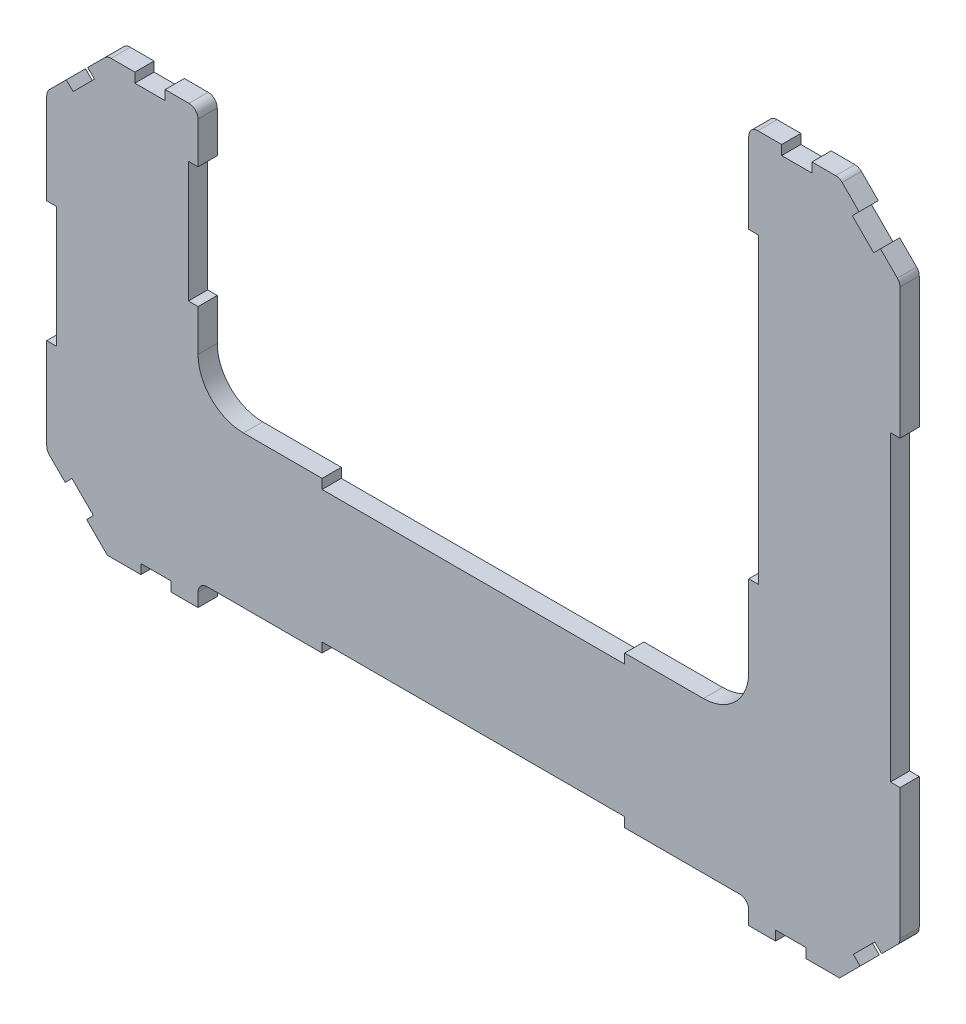
SolidWorks part; units mm, degrees
material "Cedar"
ref_plane "Front Plane" through (0, 0, 0) normal (0, 0, 1) x (1, 0, 0)
ref_plane "Top Plane" through (0, 0, 0) normal (0, 1, 0) x (1, 0, 0)
ref_plane "Right Plane" through (0, 0, 0) normal (1, 0, 0) x (0, 0, -1)
sketch "Sketch2" plane through (0, 0, 0) normal (0, 0, 1) x (1, 0, 0)
  line L0 (-141, 85.3385) -> (-91, 85.3385)
  line L1 (-91, 85.3385) -> (-91, 0)
  line L2 (-91, 0) -> (91, 0)
  line L3 (91, 0) -> (91, 171.5)
  line L4 (91, 171.5) -> (141, 171.5)
  line L5 (141, 171.5) -> (141, -57.5)
  line L6 (141, -57.5) -> (91, -57.5)
  line L7 (91, -57.5) -> (91, -50)
  line L8 (91, -50) -> (-91, -50)
  line L9 (-91, -50) -> (-91, -57.5)
  line L10 (-91, -57.5) -> (-141, -57.5)
  line L11 (-141, -57.5) -> (-141, 85.3385)
  line L12 (-31, 0) -> (-31, 124) construction
  point P10 (-31, 0)
  point P14 (91, 124)
  point P15 (-31, 85.3385)
  dimension "D1" = 124
  dimension "D2" = 122
  dimension "D3" = 60
  dimension "D4" = 47.5
  dimension "D5" = 50
  dimension "D6" = 50
  dimension "D7" = 7.5
extrude "Boss-Extrude1" add sketch "Sketch2" along normal blind 3.175 and the other way blind 3.175
chamfer "Chamfer1" distance 20 angle 45 4 edges at (-141, -57.5, 0) (141, -57.5, 0) (141, 171.5, 0) (-141, 85.3385, 0)
fillet "Fillet1" radius 15 2 edges at (91, 0, 0) (-91, 0, 0)
fillet "Fillet2" radius 3 10 edges at (141, -37.5, 0) (91, -50, 0) (-91, -50, 0) (-141, -37.5, 0) (-141, 65.3385, 0) (-121, 85.3385, 0) (-91, 85.3385, 0) (141, 151.5, 0) (121, 171.5, 0) (91, 171.5, 0)
sketch "Sketch3" plane through (0, 0, 3.175) normal (0, 0, 1) x (1, 0, 0)
  line L0 (-94.6381, 69.9757) -> (-94.6381, 14.7992)
  line L1 (-94.6381, 14.7992) -> (-97.8131, 14.7992)
  line L2 (-97.8131, 14.7992) -> (-97.8131, 69.9757)
  line L3 (-97.8131, 69.9757) -> (-94.6381, 69.9757)
  line L4 (-127.4635, 65.4691) -> (-114.3536, 78.579)
  line L5 (-114.3536, 78.579) -> (-112.1085, 76.3339)
  line L6 (-112.1085, 76.3339) -> (-125.2184, 63.2241)
  line L7 (-125.2184, 63.2241) -> (-127.4635, 65.4691)
  line L8 (-129.3392, 54.7846) -> (-126.1642, 54.7846)
  line L9 (-126.1642, 54.7846) -> (-126.1642, -28.3138)
  line L10 (-126.1642, -28.3138) -> (-129.3392, -28.3138)
  line L11 (-129.3392, -28.3138) -> (-129.3392, 54.7846)
  line L12 (-127.4635, -37.1329) -> (-125.2184, -34.8879)
  line L13 (-125.2184, -34.8879) -> (-110.9382, -49.1681)
  line L14 (-110.9382, -49.1681) -> (-113.1832, -51.4132)
  line L15 (-113.1832, -51.4132) -> (-127.4635, -37.1329)
  line L16 (-67.7784, -44.3183) -> (-67.7784, -41.1433)
  line L17 (-67.7784, -41.1433) -> (53.0181, -41.1433)
  line L18 (53.0181, -41.1433) -> (53.0181, -44.3183)
  line L19 (53.0181, -44.3183) -> (-67.7784, -44.3183)
  line L20 (114.9313, -49.5303) -> (117.1763, -51.7753)
  line L21 (117.1763, -51.7753) -> (131.7883, -37.1634)
  line L22 (131.7883, -37.1634) -> (129.5432, -34.9183)
  line L23 (129.5432, -34.9183) -> (114.9313, -49.5303)
  line L24 (-67.7784, -4.1746) -> (-67.7784, -7.3496)
  line L25 (-67.7784, -7.3496) -> (63.5847, -7.3496)
  line L26 (63.5847, -7.3496) -> (63.5847, -4.1746)
  line L27 (63.5847, -4.1746) -> (-67.7784, -4.1746)
  line L28 (92.7516, 20.9162) -> (91.2159, 151.9937)
  line L29 (91.2159, 151.9937) -> (94.3909, 151.9937)
  line L30 (94.3909, 151.9937) -> (95.9266, 20.9162)
  line L31 (95.9266, 20.9162) -> (92.7516, 20.9162)
  line L32 (96.8341, 161.8762) -> (96.8341, 158.7012)
  line L33 (96.8341, 158.7012) -> (112.5649, 158.7012)
  line L34 (112.5649, 158.7012) -> (112.5649, 161.8762)
  line L35 (112.5649, 161.8762) -> (96.8341, 161.8762)
  line L37 (117.7781, 156.4535) -> (120.0231, 158.6985)
  line L38 (120.0231, 158.6985) -> (133.8694, 144.8523)
  line L39 (133.8694, 144.8523) -> (131.6243, 142.6072)
  line L40 (131.6243, 142.6072) -> (117.7781, 156.4535)
  line L41 (129.9213, 134.1701) -> (133.0963, 134.1701)
  line L42 (133.0963, 134.1701) -> (133.0963, -24.961)
  line L43 (133.0963, -24.961) -> (129.9213, -24.961)
  line L44 (129.9213, -24.961) -> (129.9213, 134.1701)
  line L45 (121, -57.5) -> (140.1213, -38.3787) construction
  line L46 (-140.1213, -38.3787) -> (-121, -57.5) construction
  line L47 (-121.8787, 84.4598) -> (-140.1213, 66.2171) construction
  line L48 (140.1213, 152.3787) -> (121.8787, 170.6213) construction
  dimension "D1" = 3.175
extrude "Cut-Extrude1" [suppressed] cut sketch "Sketch3" against normal through all
sketch "magnets" plane through (0, 0, 3.175) normal (0, 0, 1) x (1, 0, 0)
  point P0 (94.6751, 158.4052)
  point P1 (114.7572, -50)
  point P2 (131.9288, 140.6094)
  point P3 (131.9288, -32.8111)
  point P4 (0, -44.1618)
  point P5 (-114.0039, -50)
  point P6 (-130.8821, -32.8111)
  point P9 (-130.8821, 62.3605)
  point P10 (-93.5499, 79.7316)
  point P12 (0, -4.7392)
sketch "Sketch4" plane through (0, 0, 3.175) normal (0, 0, 1) x (1, 0, 0)
  line L0 (101.8787, 171.5) -> (101.8787, 168.325)
  line L1 (119.7574, 171.5) -> (94, 171.5) construction
  line L2 (101.8787, 168.325) -> (111.8787, 168.325)
  line L3 (111.8787, 168.325) -> (111.8787, 171.5)
  line L4 (127.4645, 165.0355) -> (125.2194, 162.7905)
  line L5 (140.1213, 152.3787) -> (121.8787, 170.6213) construction
  line L6 (125.2194, 162.7905) -> (132.2905, 155.7194)
  line L7 (132.2905, 155.7194) -> (134.5355, 157.9645)
  line L8 (91, 141.75) -> (94.175, 141.75)
  line L9 (91, 168.5) -> (91, 15) construction
  line L10 (94.175, 141.75) -> (94.175, 41.75)
  line L11 (94.175, 41.75) -> (91, 41.75)
  line L12 (141, 107) -> (137.825, 107)
  line L13 (141, -36.2574) -> (141, 150.2574) construction
  line L14 (137.825, 107) -> (137.825, 7)
  line L15 (137.825, 7) -> (141, 7)
  line L16 (-50, 0) -> (-50, -3.175)
  line L17 (76, 0) -> (-76, 0) construction
  line L18 (-50, -3.175) -> (50, -3.175)
  line L19 (50, -3.175) -> (50, 0)
  line L20 (-50, -50) -> (-50, -46.825)
  line L21 (-88, -50) -> (88, -50) construction
  line L22 (-50, -46.825) -> (50, -46.825)
  line L23 (50, -46.825) -> (50, -50)
  line L24 (-137.825, -6.0808) -> (-141, -6.0808)
  line L25 (-141, 64.0958) -> (-141, -36.2574) construction
  line L26 (-137.825, 33.9192) -> (-137.825, -6.0808)
  line L27 (-137.825, 33.9192) -> (-141, 33.9192)
  line L28 (-134.5355, 71.8029) -> (-132.2905, 69.5579)
  line L29 (-121.8787, 84.4598) -> (-140.1213, 66.2171) construction
  line L30 (-132.2905, 69.5579) -> (-125.2194, 76.6289)
  line L31 (-125.2194, 76.6289) -> (-127.4645, 78.874)
  line L32 (-111.8787, 85.3385) -> (-111.8787, 82.1635)
  line L33 (-94, 85.3385) -> (-119.7574, 85.3385) construction
  line L35 (-111.8787, 82.1635) -> (-101.8787, 82.1635)
  line L36 (-91, 68.6692) -> (-94.175, 68.6692)
  line L37 (-91, 15) -> (-91, 82.3385) construction
  line L38 (-94.175, 68.6692) -> (-94.175, 28.6692)
  line L39 (-94.175, 28.6692) -> (-91, 28.6692)
  line L40 (-109.875, -57.5) -> (-109.875, -54.325)
  line L41 (-121, -57.5) -> (-91, -57.5) construction
  line L42 (-109.875, -54.325) -> (-99.875, -54.325)
  line L43 (-99.875, -54.325) -> (-99.875, -57.5)
  line L44 (99.875, -57.5) -> (99.875, -54.325)
  line L45 (91, -57.5) -> (121, -57.5) construction
  line L46 (99.875, -54.325) -> (109.875, -54.325)
  line L47 (109.875, -54.325) -> (109.875, -57.5)
  line L48 (-134.8917, -43.6083) -> (-132.6466, -41.3632)
  line L49 (-140.1213, -38.3787) -> (-121, -57.5) construction
  line L50 (-132.6466, -41.3632) -> (-125.5756, -48.4343)
  line L51 (-125.5756, -48.4343) -> (-127.8206, -50.6794)
  line L52 (127.8206, -50.6794) -> (125.5756, -48.4343)
  line L53 (121, -57.5) -> (140.1213, -38.3787) construction
  line L54 (125.5756, -48.4343) -> (132.6466, -41.3632)
  line L55 (132.6466, -41.3632) -> (134.8917, -43.6083)
  line L56 (-131.3562, -47.1438) -> (-129.1111, -44.8988) construction
  line L57 (-104.875, -57.5) -> (-104.875, -54.325)
  line L58 (104.875, -57.5) -> (104.875, -54.325)
  line L59 (-131, 75.3385) -> (-128.7549, 73.0934) construction
  line L60 (-106.8787, 82.1635) -> (-106.8787, 85.3385) construction
  line L61 (128.7549, 159.2549) -> (131, 161.5) construction
  line L62 (129.1111, -44.8988) -> (131.3562, -47.1438) construction
  line L63 (91, -57.5) -> (118.75, -57.5) construction
  line L64 (122.591, -55.909) -> (140.1213, -38.3787) construction
  line L65 (122.591, -55.909) -> (121, -57.5) construction
  line L66 (121, -57.5) -> (118.75, -57.5) construction
  line L67 (-91, -57.5) -> (-118.75, -57.5) construction
  line L68 (-118.75, -57.5) -> (-121, -57.5) construction
  line L69 (-121, -57.5) -> (-122.591, -55.909) construction
  line L70 (-122.591, -55.909) -> (-140.1213, -38.3787) construction
  line L71 (-101.8787, 82.1635) -> (-101.8787, 85.3385)
  point P95 (0, -46.825)
  point P97 (0, -50)
  point P99 (0, -3.175)
  point P101 (137.825, 57)
  point P103 (141, 57)
  point P104 (94.175, 91.75)
  point P105 (91, 91.75)
  point P106 (106.8787, 168.325)
  point P107 (106.8787, 171.5)
  point P108 (131, 161.5)
  point P109 (128.7549, 159.2549)
  point P112 (-137.825, 13.9192)
  point P113 (-141, 13.9192)
  point P114 (-94.175, 48.6692)
  point P115 (-91, 48.6692)
  point P116 (129.1111, -44.8988)
  point P117 (130.5607, -47.9393)
  line M1 (121, -57.5) -> (140.1213, -38.3787)
  line M3 (141, -36.2574) -> (141, 150.2574)
  line M5 (140.1213, 152.3787) -> (121.8787, 170.6213)
  line M7 (119.7574, 171.5) -> (94, 171.5)
  line M9 (91, 168.5) -> (91, 15)
  line M11 (76, 0) -> (-76, 0)
  line M13 (-91, 15) -> (-91, 82.3385)
  line M15 (-94, 85.3385) -> (-119.7574, 85.3385)
  line M17 (-121.8787, 84.4598) -> (-140.1213, 66.2171)
  line M19 (-141, 64.0958) -> (-141, -36.2574)
  line M21 (-140.1213, -38.3787) -> (-121, -57.5)
  line M22 (-121, -57.5) -> (-91, -57.5)
  line M25 (-88, -50) -> (88, -50)
  line M28 (91, -57.5) -> (121, -57.5)
  dimension "D1" = 3.175
  dimension "D5" = 100
  dimension "D6" = 100
  dimension "D7" = 100
  dimension "D8" = 100
  dimension "D4" = 10
  dimension "D2" = 10
  dimension "D10" = 2.25
  dimension "D3" = 2.25
  dimension "D11" = 10
  dimension "D13" = 3.175
  dimension "D12" = 10
  dimension "D14" = 10
  dimension "D15" = 10
  dimension "D16" = 10
  dimension "D17" = 10
  dimension "D18" = 40
  dimension "D19" = 3.175
extrude "wall_slots" cut sketch "Sketch4" against normal blind 60 contours L26 L27 L24 M19 | L18 L19 L16 M11 | L23 L22 L20 M25 | L51 L50 L48 M21 | L57 L43 L42 M22 | L57 L42 L40 M22 | L38 L39 L36 M13 | L35 L71 L32 M15 | L30 L31 L28 M17 | L58 L47 L46 M28 | L58 L46 L44 M28 | L55 L54 L52 M1 | L14 L15 L12 M3 | L11 L10 L8 M9 | L2 L3 L0 M7 | L6 L7 L4 M5 region at (106.8787, 169.9125, 3.175) region at (129.8775, 160.3775, 3.175) region at (92.5875, 91.75, 3.175) region at (139.4125, 57, 3.175) region at (0, -1.5875, 3.175) region at (0, -48.4125, 3.175) region at (-139.4125, 13.9192, 3.175) region at (-129.8775, 74.2159, 3.175) region at (-106.8787, 83.751, 3.175) region at (-92.5875, 48.6692, 3.175) region at (-130.2336, -46.0213, 3.175) region at (-107.375, -55.9125, 3.175) region at (-102.375, -55.9125, 3.175) region at (130.2336, -46.0213, 3.175) region at (102.375, -55.9125, 3.175) region at (107.375, -55.9125, 3.175)
sketch "wall_measure" plane through (0, 0, 3.175) normal (0, 0, 1) x (1, 0, 0)
  line L0 (-119.7574, 85.3385) -> (-119.7574, 82.1635)
  line L1 (-119.7574, 82.1635) -> (-94, 82.1635)
  line L2 (-94, 82.1635) -> (-94, 85.3385)
  line L4 (94, 171.5) -> (94, 168.325)
  line L5 (94, 168.325) -> (119.7574, 168.325)
  line L6 (119.7574, 168.325) -> (119.7574, 171.5)
  line L7 (101.8787, 168.325) -> (111.8787, 168.325) construction
  line L8 (121.8787, 170.6213) -> (119.6336, 168.3763)
  line L9 (119.6336, 168.3763) -> (137.8763, 150.1336)
  line L10 (137.8763, 150.1336) -> (140.1213, 152.3787)
  line L11 (140.1213, 152.3787) -> (134.5355, 157.9645) construction
  line L12 (91, 168.5) -> (94.175, 168.5)
  line L13 (94.175, 168.5) -> (94.175, 15)
  line L14 (94.175, 15) -> (91, 15)
  line L15 (91, 41.75) -> (91, 15) construction
  line L16 (141, 150.2574) -> (137.825, 150.2574)
  line L17 (137.825, 150.2574) -> (137.825, -36.2574)
  line L18 (137.825, -36.2574) -> (141, -36.2574)
  line L19 (-76, 0) -> (-76, -3.175)
  line L20 (-76, -3.175) -> (76, -3.175)
  line L21 (76, -3.175) -> (76, 0)
  line L22 (-88, -50) -> (-88, -46.825)
  line L23 (-88, -46.825) -> (88, -46.825)
  line L24 (88, -46.825) -> (88, -50)
  line L25 (91, -53) -> (117.9584, -53)
  line L26 (117.9584, -53) -> (117.9584, -57.5)
  line L27 (140.1213, -38.3787) -> (137.8763, -36.1336)
  line L28 (137.8763, -36.1336) -> (120.9057, -53.1042)
  line L29 (120.9057, -53.1042) -> (123.1508, -55.3492)
  line L30 (121, -57.5) -> (127.8206, -50.6794) construction
  line L31 (125.5756, -48.4343) -> (132.6466, -41.3632) construction
  line L32 (117.9584, -57.5) -> (121, -57.5) construction
  line L33 (121, -57.5) -> (123.1508, -55.3492) construction
  line L34 (-141, 64.0958) -> (-138, 64.0958)
  line L35 (-138, 64.0958) -> (-138, -36.2574)
  line L36 (-138, -36.2574) -> (-141, -36.2574)
  line L37 (-91, 82.3385) -> (-94.175, 82.3385)
  line L38 (-94.175, 82.3385) -> (-94.175, 15)
  line L39 (-94.175, 15) -> (-91, 15)
  line L40 (-50, -46.825) -> (50, -46.825) construction
  line L41 (-50, -3.175) -> (50, -3.175) construction
  line L42 (137.825, 107) -> (137.825, 7) construction
  line L43 (94.175, 141.75) -> (94.175, 41.75) construction
  line L44 (125.2194, 162.7905) -> (132.2905, 155.7194) construction
  line L45 (-94.175, 68.6692) -> (-94.175, 28.6692) construction
  line L47 (-111.8787, 82.1635) -> (-101.8787, 82.1635) construction
  arc A0 (76, 0) -> (91, 15) centre (76, 15) ccw construction
  arc A1 (-91, 15) -> (-76, 0) centre (-76, 15) ccw construction
  dimension "D1" = 25.7574
  dimension "D2" = 25.7574
  dimension "D3" = 25.799
  dimension "D4" = 153.5
  dimension "D5" = 186.5147
  dimension "D6" = 152
  dimension "D7" = 176
  dimension "D8" = 24
  dimension "D9" = 3.0416
  dimension "D10" = 26.9584
  dimension "D11" = 100.3532
  dimension "D12" = 67.3385
sketch "Sketch5" plane through (0, 0, 3.175) normal (0, 0, 1) x (1, 0, 0)
  line L72 (132.2905, 155.7194) -> (125.2194, 162.7905)
  line L73 (125.2194, 162.7905) -> (127.4645, 165.0355)
  line L74 (127.4645, 165.0355) -> (121.8787, 170.6213)
  line L75 (119.7574, 171.5) -> (111.8787, 171.5)
  line L76 (111.8787, 171.5) -> (111.8787, 168.325)
  line L77 (111.8787, 168.325) -> (101.8787, 168.325)
  line L78 (101.8787, 168.325) -> (101.8787, 171.5)
  line L79 (101.8787, 171.5) -> (94, 171.5)
  line L80 (91, 168.5) -> (91, 141.75)
  line L81 (91, 141.75) -> (94.175, 141.75)
  line L82 (94.175, 141.75) -> (94.175, 41.75)
  line L83 (94.175, 41.75) -> (91, 41.75)
  line L84 (91, 41.75) -> (91, 15)
  line L85 (76, 0) -> (50, 0)
  line L86 (50, 0) -> (50, -3.175)
  line L87 (50, -3.175) -> (-50, -3.175)
  line L88 (-50, -3.175) -> (-50, 0)
  line L89 (-50, 0) -> (-76, 0)
  line L90 (-91, 15) -> (-91, 28.6692)
  line L91 (-91, 28.6692) -> (-94.175, 28.6692)
  line L92 (-94.175, 28.6692) -> (-94.175, 68.6692)
  line L93 (-94.175, 68.6692) -> (-91, 68.6692)
  line L94 (-91, 68.6692) -> (-91, 82.3385)
  line L95 (-94, 85.3385) -> (-101.8787, 85.3385)
  line L96 (-101.8787, 85.3385) -> (-101.8787, 82.1635)
  line L97 (-101.8787, 82.1635) -> (-111.8787, 82.1635)
  line L98 (-111.8787, 82.1635) -> (-111.8787, 85.3385)
  line L99 (-111.8787, 85.3385) -> (-119.7574, 85.3385)
  line L100 (-121.8787, 84.4598) -> (-127.4645, 78.874)
  line L101 (-127.4645, 78.874) -> (-125.2194, 76.6289)
  line L102 (-125.2194, 76.6289) -> (-132.2905, 69.5579)
  line L103 (-132.2905, 69.5579) -> (-134.5355, 71.8029)
  line L104 (-134.5355, 71.8029) -> (-140.1213, 66.2171)
  line L105 (-141, 64.0958) -> (-141, 33.9192)
  line L106 (-141, 33.9192) -> (-137.825, 33.9192)
  line L107 (-137.825, 33.9192) -> (-137.825, -6.0808)
  line L108 (-137.825, -6.0808) -> (-141, -6.0808)
  line L109 (-141, -6.0808) -> (-141, -36.2574)
  line L110 (-140.1213, -38.3787) -> (-134.8917, -43.6083)
  line L111 (-134.8917, -43.6083) -> (-132.6466, -41.3632)
  line L112 (-132.6466, -41.3632) -> (-125.5756, -48.4343)
  line L113 (-125.5756, -48.4343) -> (-127.8206, -50.6794)
  line L114 (-127.8206, -50.6794) -> (-121, -57.5)
  line L115 (-121, -57.5) -> (-109.875, -57.5)
  line L116 (-109.875, -57.5) -> (-109.875, -54.325)
  line L117 (-109.875, -54.325) -> (-99.875, -54.325)
  line L118 (-99.875, -54.325) -> (-99.875, -57.5)
  line L119 (-99.875, -57.5) -> (-91, -57.5)
  line L120 (-91, -57.5) -> (-91, -53)
  line L121 (-88, -50) -> (-50, -50)
  line L122 (-50, -50) -> (-50, -46.825)
  line L123 (-50, -46.825) -> (50, -46.825)
  line L124 (50, -46.825) -> (50, -50)
  line L125 (50, -50) -> (88, -50)
  line L126 (91, -53) -> (91, -57.5)
  line L127 (91, -57.5) -> (99.875, -57.5)
  line L128 (99.875, -57.5) -> (99.875, -54.325)
  line L129 (99.875, -54.325) -> (109.875, -54.325)
  line L130 (109.875, -54.325) -> (109.875, -57.5)
  line L131 (109.875, -57.5) -> (121, -57.5)
  line L132 (121, -57.5) -> (127.8206, -50.6794)
  line L133 (127.8206, -50.6794) -> (125.5756, -48.4343)
  line L134 (125.5756, -48.4343) -> (132.6466, -41.3632)
  line L135 (132.6466, -41.3632) -> (134.8917, -43.6083)
  line L136 (134.8917, -43.6083) -> (140.1213, -38.3787)
  line L137 (141, -36.2574) -> (141, 7)
  line L138 (141, 7) -> (137.825, 7)
  line L139 (137.825, 7) -> (137.825, 107)
  line L140 (137.825, 107) -> (141, 107)
  line L141 (141, 107) -> (141, 150.2574)
  line L142 (140.1213, 152.3787) -> (134.5355, 157.9645)
  line L143 (134.5355, 157.9645) -> (132.2905, 155.7194)
  line L144 (132.2905, 155.7194) -> (125.2194, 162.7905)
  line L145 (125.2194, 162.7905) -> (127.4645, 165.0355)
  line L146 (127.4645, 165.0355) -> (121.8787, 170.6213)
  line L147 (119.7574, 171.5) -> (111.8787, 171.5)
  line L148 (111.8787, 171.5) -> (111.8787, 168.325)
  line L149 (111.8787, 168.325) -> (101.8787, 168.325)
  line L150 (101.8787, 168.325) -> (101.8787, 171.5)
  line L151 (101.8787, 171.5) -> (94, 171.5)
  line L152 (91, 168.5) -> (91, 141.75)
  line L153 (91, 141.75) -> (94.175, 141.75)
  line L154 (94.175, 141.75) -> (94.175, 41.75)
  line L155 (94.175, 41.75) -> (91, 41.75)
  line L156 (91, 41.75) -> (91, 15)
  line L157 (76, 0) -> (50, 0)
  line L158 (50, 0) -> (50, -3.175)
  line L159 (50, -3.175) -> (-50, -3.175)
  line L160 (-50, -3.175) -> (-50, 0)
  line L161 (-50, 0) -> (-76, 0)
  line L162 (-91, 15) -> (-91, 28.6692)
  line L163 (-91, 28.6692) -> (-94.175, 28.6692)
  line L164 (-94.175, 28.6692) -> (-94.175, 68.6692)
  line L165 (-94.175, 68.6692) -> (-91, 68.6692)
  line L166 (-91, 68.6692) -> (-91, 82.3385)
  line L167 (-94, 85.3385) -> (-101.8787, 85.3385)
  line L168 (-101.8787, 85.3385) -> (-101.8787, 82.1635)
  line L169 (-101.8787, 82.1635) -> (-111.8787, 82.1635)
  line L170 (-111.8787, 82.1635) -> (-111.8787, 85.3385)
  line L171 (-111.8787, 85.3385) -> (-119.7574, 85.3385)
  line L172 (-121.8787, 84.4598) -> (-127.4645, 78.874)
  line L173 (-127.4645, 78.874) -> (-125.2194, 76.6289)
  line L174 (-125.2194, 76.6289) -> (-132.2905, 69.5579)
  line L175 (-132.2905, 69.5579) -> (-134.5355, 71.8029)
  line L176 (-134.5355, 71.8029) -> (-140.1213, 66.2171)
  line L177 (-141, 64.0958) -> (-141, 33.9192)
  line L178 (-141, 33.9192) -> (-137.825, 33.9192)
  line L179 (-137.825, 33.9192) -> (-137.825, -6.0808)
  line L180 (-137.825, -6.0808) -> (-141, -6.0808)
  line L181 (-141, -6.0808) -> (-141, -36.2574)
  line L182 (-140.1213, -38.3787) -> (-134.8917, -43.6083)
  line L183 (-134.8917, -43.6083) -> (-132.6466, -41.3632)
  line L184 (-132.6466, -41.3632) -> (-125.5756, -48.4343)
  line L185 (-125.5756, -48.4343) -> (-127.8206, -50.6794)
  line L186 (-127.8206, -50.6794) -> (-121, -57.5)
  line L187 (-121, -57.5) -> (-109.875, -57.5)
  line L188 (-109.875, -57.5) -> (-109.875, -54.325)
  line L189 (-109.875, -54.325) -> (-99.875, -54.325)
  line L190 (-99.875, -54.325) -> (-99.875, -57.5)
  line L191 (-99.875, -57.5) -> (-91, -57.5)
  line L192 (-91, -57.5) -> (-91, -53)
  line L193 (-88, -50) -> (-50, -50)
  line L194 (-50, -50) -> (-50, -46.825)
  line L195 (-50, -46.825) -> (50, -46.825)
  line L196 (50, -46.825) -> (50, -50)
  line L197 (50, -50) -> (88, -50)
  line L198 (91, -53) -> (91, -57.5)
  line L199 (91, -57.5) -> (99.875, -57.5)
  line L200 (99.875, -57.5) -> (99.875, -54.325)
  line L201 (99.875, -54.325) -> (109.875, -54.325)
  line L202 (109.875, -54.325) -> (109.875, -57.5)
  line L203 (109.875, -57.5) -> (121, -57.5)
  line L204 (121, -57.5) -> (127.8206, -50.6794)
  line L205 (127.8206, -50.6794) -> (125.5756, -48.4343)
  line L206 (125.5756, -48.4343) -> (132.6466, -41.3632)
  line L207 (132.6466, -41.3632) -> (134.8917, -43.6083)
  line L208 (134.8917, -43.6083) -> (140.1213, -38.3787)
  line L209 (141, -36.2574) -> (141, 7)
  line L210 (141, 7) -> (137.825, 7)
  line L211 (137.825, 7) -> (137.825, 107)
  line L212 (137.825, 107) -> (141, 107)
  line L213 (141, 107) -> (141, 150.2574)
  line L214 (140.1213, 152.3787) -> (134.5355, 157.9645)
  line L215 (134.5355, 157.9645) -> (132.2905, 155.7194)
  arc A12 (121.8787, 170.6213) -> (119.7574, 171.5) centre (119.7574, 168.5) ccw
  arc A13 (94, 171.5) -> (91, 168.5) centre (94, 168.5) ccw
  arc A14 (76, 0) -> (91, 15) centre (76, 15) ccw
  arc A15 (-91, 15) -> (-76, 0) centre (-76, 15) ccw
  arc A16 (-91, 82.3385) -> (-94, 85.3385) centre (-94, 82.3385) ccw
  arc A17 (-119.7574, 85.3385) -> (-121.8787, 84.4598) centre (-119.7574, 82.3385) ccw
  arc A18 (-140.1213, 66.2171) -> (-141, 64.0958) centre (-138, 64.0958) ccw
  arc A19 (-141, -36.2574) -> (-140.1213, -38.3787) centre (-138, -36.2574) ccw
  arc A20 (-88, -50) -> (-91, -53) centre (-88, -53) ccw
  arc A21 (91, -53) -> (88, -50) centre (88, -53) ccw
  arc A22 (140.1213, -38.3787) -> (141, -36.2574) centre (138, -36.2574) ccw
  arc A23 (141, 150.2574) -> (140.1213, 152.3787) centre (138, 150.2574) ccw
  arc A24 (121.8787, 170.6213) -> (119.7574, 171.5) centre (119.7574, 168.5) ccw
  arc A25 (94, 171.5) -> (91, 168.5) centre (94, 168.5) ccw
  arc A26 (76, 0) -> (91, 15) centre (76, 15) ccw
  arc A27 (-91, 15) -> (-76, 0) centre (-76, 15) ccw
  arc A28 (-91, 82.3385) -> (-94, 85.3385) centre (-94, 82.3385) ccw
  arc A29 (-119.7574, 85.3385) -> (-121.8787, 84.4598) centre (-119.7574, 82.3385) ccw
  arc A30 (-140.1213, 66.2171) -> (-141, 64.0958) centre (-138, 64.0958) ccw
  arc A31 (-141, -36.2574) -> (-140.1213, -38.3787) centre (-138, -36.2574) ccw
  arc A32 (-88, -50) -> (-91, -53) centre (-88, -53) ccw
  arc A33 (91, -53) -> (88, -50) centre (88, -53) ccw
  arc A34 (140.1213, -38.3787) -> (141, -36.2574) centre (138, -36.2574) ccw
  arc A35 (141, 150.2574) -> (140.1213, 152.3787) centre (138, 150.2574) ccw
  dimension "D1" = 0
equation "\"dX\"= 122mm"
equation "\"dY\"= 124mm"
equation "\"hmotor\"= 50mm"
equation "\"D1@Sketch2\"=\"dY\""
equation "\"D2@Sketch2\"=\"dX\""
equation "\"D5@Sketch2\"=\"hmotor\""
equation "\"D6@Sketch2\"=\"hmotor\""
equation "\"t_wood\"= 0.25in"
equation "\"D1@Boss-Extrude1\"=\"t_wood\"/2"
equation "\"D2@Boss-Extrude1\"=\"t_wood\"/2"
equation "\"D1@Sketch3\"=\"t_wood\"/2"
equation "\"D1@Sketch4\"=\"t_wood\"/2"
equation "\"D13@Sketch4\"=\"t_wood\"/2"
equation "\"D19@Sketch4\"=\"t_wood\"/2"
